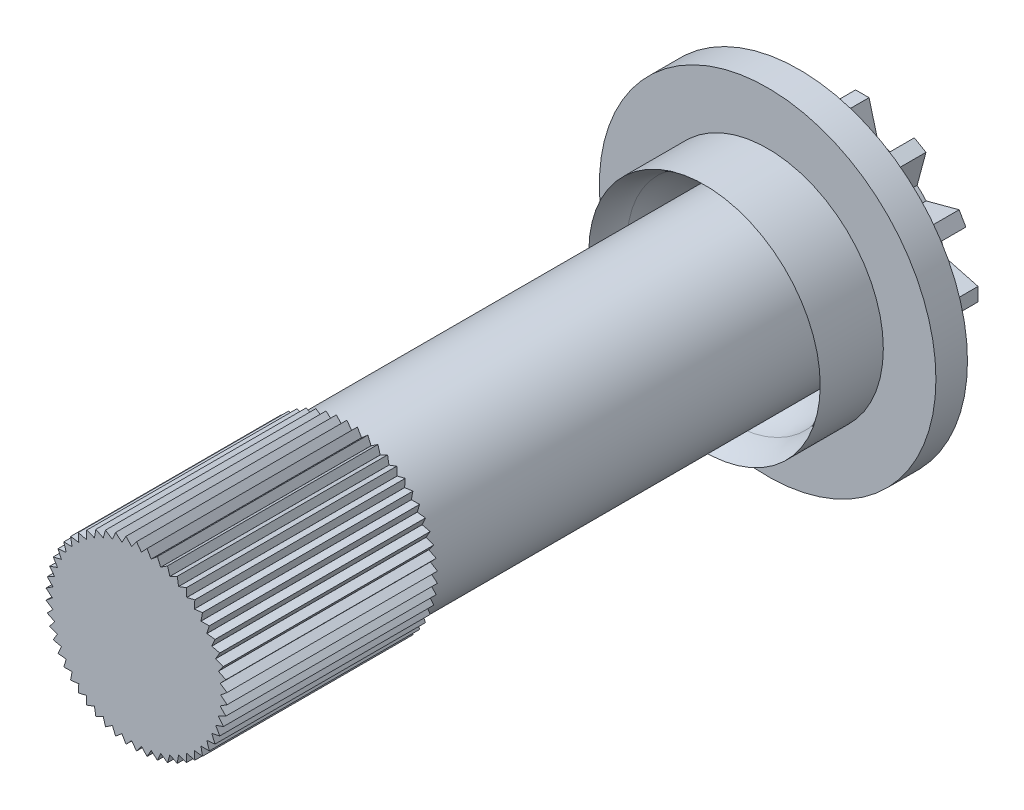
SolidWorks part; units mm, degrees
ref_plane "Front Plane" through (0, 0, 0) normal (0, 0, 1) x (1, 0, 0)
ref_plane "Top Plane" through (0, 0, 0) normal (0, 1, 0) x (1, 0, 0)
ref_plane "Right Plane" through (0, 0, 0) normal (1, 0, 0) x (0, 0, -1)
sketch "Sketch1" plane through (0, 0, 0) normal (0, 0, 1) x (1, 0, 0)
  circle A0 centre (0, 0) radius 4
extrude "Boss-Extrude1" add sketch "Sketch1" along normal blind 3
sketch "Sketch2" plane through (0, 0, 0) normal (0, 0, -1) x (-1, 0, 0)
  line L0 (0, 0) -> (0, 7.1761) construction
  line L1 (0, 5.5) -> (-0.32, 5.5)
  line L2 (-0.32, 5.5) -> (-0.7648, 3.84)
  line L3 (-0.7648, 3.84) -> (0.7648, 3.84)
  line L4 (0.7648, 3.84) -> (0.32, 5.5)
  line L5 (0, 5.5) -> (0.32, 5.5)
  point P5 (-0.16, 5.5)
  dimension "D1" = 75
  dimension "D2" = 75
  dimension "D3" = 5.5
  dimension "D4" = 3.84
  dimension "D5" = 0.32
  dimension "D6" = 0.32
extrude "Boss-Extrude2" add sketch "Sketch2" against normal blind 3
pattern_circular "CirPattern1" count 12 over 360 about axis through (0, 0, 3) along (0, 0, -1) of "Boss-Extrude2"
ref_plane "Plane1" through (0, 0, 3) normal (0, 0, 1) x (1, 0, 0)
sketch "Sketch3" plane through (0, 0, 3) normal (0, 0, 1) x (1, 0, 0)
  circle A0 centre (0, 0) radius 8
extrude "Boss-Extrude3" add sketch "Sketch3" along normal blind 1.5
ref_plane "Plane2" through (0, 0, 4.5) normal (0, 0, 1) x (1, 0, 0)
sketch "Sketch4" plane through (0, 0, 4.5) normal (0, 0, 1) x (1, 0, 0)
  circle A0 centre (0, 0) radius 4
extrude "Boss-Extrude4" add sketch "Sketch4" along normal blind 30
ref_plane "Plane3" through (0, 0, 34.5) normal (0, 0, 1) x (1, 0, 0)
sketch "Sketch5" plane through (0, 0, 34.5) normal (0, 0, 1) x (1, 0, 0)
  line L0 (-0.3751, 3.7972) -> (0, 4.3107)
  line L1 (0, 0) -> (0, 8.312) construction
  line L2 (0.3751, 3.7972) -> (0, 4.3107)
  line L3 (-0.3751, 3.7972) -> (0.3751, 3.7972)
extrude "Boss-Extrude5" add sketch "Sketch5" against normal blind 10
pattern_circular "CirPattern2" count 54 over 360 about axis through (0, 0, 34.5) along (0, 0, -1) of "Boss-Extrude5"
sketch "Sketch6" plane through (0, 0, 4.5) normal (0, 0, 1) x (1, 0, 0)
  circle A0 centre (0, 0) radius 5.5
  circle A1 centre (0, 0) radius 5
extrude "Boss-Extrude6" add sketch "Sketch6" along normal blind 3
fillet "Fillet3" radius 3 1 edges at (5, 0, 4.5)
fillet "Fillet4" radius 3 1 edges at (5, 0, 7.5)
